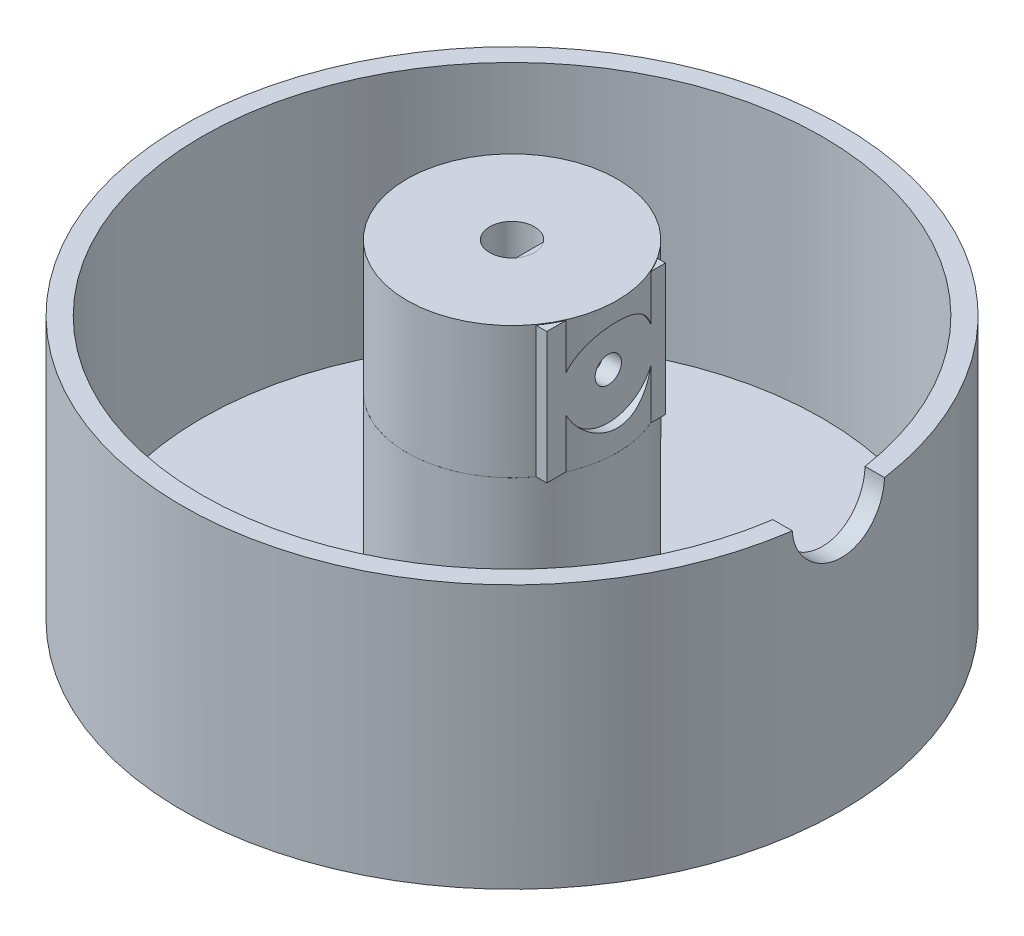
SolidWorks part; units mm, degrees
ref_plane "Front Plane" through (0, 0, 0) normal (0, 0, 1) x (1, 0, 0)
ref_plane "Top Plane" through (0, 0, 0) normal (0, 1, 0) x (1, 0, 0)
ref_plane "Right Plane" through (0, 0, 0) normal (1, 0, 0) x (0, 0, -1)
sketch "Sketch1" plane through (0, 0, 0) normal (0, 1, 0) x (1, 0, 0)
  circle A0 centre (0, 0) radius 15.958
extrude "Boss-Extrude1" add sketch "Sketch1" along normal blind 20
sketch "Sketch2" plane through (0, 20, 0) normal (0, 1, 0) x (1, 0, 0)
  circle A0 centre (0, 0) radius 3.4
extrude "Cut-Extrude1" cut sketch "Sketch2" against normal blind 13.55 contours A0
ref_plane "Plane1" through (0, 18.26, 0) normal (0, 1, 0) x (1, 0, 0)
ref_axis "Axis1" through (0, 6.45, 0) along (0, 1, 0)
ref_point "Point2"
sketch "Sketch5" plane through (0, 18.26, 0) normal (0, 1, 0) x (1, 0, 0)
  line L0 (0, 0) -> (2.6, 0) construction
  line L2 (2.6, -3.5716) -> (4.1507, -3.5716)
  line L3 (2.6, -3.5716) -> (2.6, 3.6126)
  line L4 (2.6, 3.6126) -> (4.1507, 3.6126)
  line L5 (4.1507, -3.5716) -> (4.1507, 3.6126)
extrude "Boss-Extrude2" add sketch "Sketch5" against normal blind 13.55
sketch "Sketch7" plane through (2.6, 0, 0) normal (-1, 0, 0) x (0, 0, 1)
  line L1 (-8.6717, 19.91) -> (9.3323, 19.91)
  line L2 (-8.6717, 19.91) -> (-8.6717, 0)
  line L3 (-8.6717, 0) -> (9.3323, 0)
  line L4 (9.3323, 19.91) -> (9.3323, 0)
extrude "Boss-Extrude3" add sketch "Sketch7" against normal blind 12
sketch "Sketch6" plane through (2.6, 0, 0) normal (-1, 0, 0) x (0, 0, 1)
  line L1 (-2.1909, 6.45) -> (-2.1909, 19.91) construction
  line L2 (2.1909, 19.91) -> (2.1909, 6.45) construction
  line L3 (-2.1909, 15.4522) -> (2.1909, 15.4522) construction
  circle A0 centre (0, 10.2369) radius 2
extrude "Cut-Extrude2" cut sketch "Sketch6" against normal blind 13.55 and the other way blind 1
ref_axis "Axis2" through (-1.8994, 10.2369, 0) along (-1, 0, 0)
ref_axis "Axis4" through (15.958, 10.2369, 0) along (-1, 0, 0)
ref_plane "Plane3" through (0, 0, 0) normal (0, 0, 1) x (1, 0, 0)
sketch "Sketch9" plane through (0, 0, 0) normal (0, 0, 1) x (1, 0, 0)
  line L0 (11.8765, 10.2369) -> (11.8765, 5.8619)
  line L1 (4.9434, 5.8619) -> (11.8765, 5.8619)
  line L2 (4.9434, 5.8619) -> (4.9434, 10.2369)
  line L3 (4.9434, 10.2369) -> (4.9434, 14.6143)
  line L4 (4.9434, 14.6143) -> (11.8765, 14.6143)
  line L5 (11.8765, 14.6143) -> (11.8765, 10.2369)
  line L6 (15.958, 10.2369) -> (2.6, 10.2369) construction
  line L7 (4.9434, 14.6143) -> (11.8765, 5.8619) construction
extrude "NutOpening" cut sketch "Sketch9" against normal blind 30
sketch "Sketch10" plane through (0, 0, 0) normal (0, -1, 0) x (1, 0, 0)
  circle A0 centre (0, 0) radius 50
extrude "Boss-Extrude4" add sketch "Sketch10" along normal blind 30
sketch "Sketch11" plane through (0, 0, 0) normal (0, 1, 0) x (1, 0, 0)
  line L1 (31.7817, 38.8528) -> (14.4942, 48.0577) construction
  line L2 (14.4942, 48.0577) -> (-5, 49.9462) construction
  line L3 (-5, 49.9462) -> (-23.733, 44.2308) construction
  line L4 (-23.733, 44.2308) -> (-38.8528, 31.7817) construction
  line L5 (-38.8528, 31.7817) -> (-48.0577, 14.4942) construction
  line L6 (-48.0577, 14.4942) -> (-49.9462, -5) construction
  line L7 (-49.9462, -5) -> (-44.2308, -23.733) construction
  line L8 (-44.2308, -23.733) -> (-31.7817, -38.8528) construction
  line L9 (-31.7817, -38.8528) -> (-14.4942, -48.0577) construction
  line L10 (-14.4942, -48.0577) -> (5, -49.9462) construction
  line L11 (5, -49.9462) -> (23.733, -44.2308) construction
  line L12 (23.733, -44.2308) -> (38.8528, -31.7817) construction
  line L13 (38.8528, -31.7817) -> (48.0577, -14.4942) construction
  line L14 (48.0577, -14.4942) -> (49.9462, 5) construction
  line L15 (49.9462, 5) -> (44.2308, 23.733) construction
  line L16 (44.2308, 23.733) -> (31.7817, 38.8528) construction
  circle A0 centre (0, 0) radius 49.2313 construction
  circle A1 centre (5, -49.9462) radius 5
  circle A2 centre (-14.4942, -48.0577) radius 5
  circle A3 centre (-31.7817, -38.8528) radius 5
  circle A4 centre (-44.2308, -23.733) radius 5
  circle A5 centre (-49.9462, -5) radius 5
  circle A6 centre (-48.0577, 14.4942) radius 5
  circle A7 centre (-38.8528, 31.7817) radius 5
  circle A8 centre (-23.733, 44.2308) radius 5
  circle A9 centre (-5, 49.9462) radius 5
  circle A10 centre (14.4942, 48.0577) radius 5
  circle A11 centre (31.7817, 38.8528) radius 5
  circle A12 centre (44.2308, 23.733) radius 5
  circle A13 centre (49.9462, 5) radius 5
  circle A14 centre (48.0577, -14.4942) radius 5
  circle A15 centre (38.8528, -31.7817) radius 5
  circle A16 centre (23.733, -44.2308) radius 5
sketch "Sketch12" plane through (0, 0, 0) normal (0, 1, 0) x (1, 0, 0)
  circle A0 centre (0, 0) radius 47.0828
  circle A1 centre (0, 0) radius 15.9579
extrude "Cut-Extrude5" cut sketch "Sketch12" against normal offset from surface (27 mm away) 3 up to face at (0, -30, -50)
sketch "Sketch13" plane through (0, 0, 0) normal (0, 1, 0) x (1, 0, 0)
  circle A0 centre (0, 0) radius 47.0828
  circle A1 centre (0, 0) radius 50
extrude "Boss-Extrude5" add sketch "Sketch13" along normal blind 10
sketch "Sketch14" plane through (11.8765, 0, 0) normal (-1, 0, 0) x (0, 0, 1)
  line L1 (-5.0541, 10.2369) -> (-2.5271, 5.8599)
  line L2 (-2.5271, 5.8599) -> (2.5271, 5.8599)
  line L3 (2.5271, 5.8599) -> (5.0541, 10.2369)
  line L4 (5.0541, 10.2369) -> (2.5271, 14.6139)
  line L5 (2.5271, 14.6139) -> (-2.5271, 14.6139)
  line L6 (-2.5271, 14.6139) -> (-5.0541, 10.2369)
  circle A0 centre (0, 10.2369) radius 4.377 construction
extrude "Cut-Extrude6" cut sketch "Sketch14" along normal up to surface (6.9331 mm away) up to face at (4.9434, 10.2377, -5.391)
sketch "Sketch16" plane through (14.6, 0, 0) normal (1, 0, 0) x (0, 0, -1)
  circle A0 centre (0, 10.2369) radius 7
extrude "Cut-Extrude7" cut sketch "Sketch16" along normal blind 40
